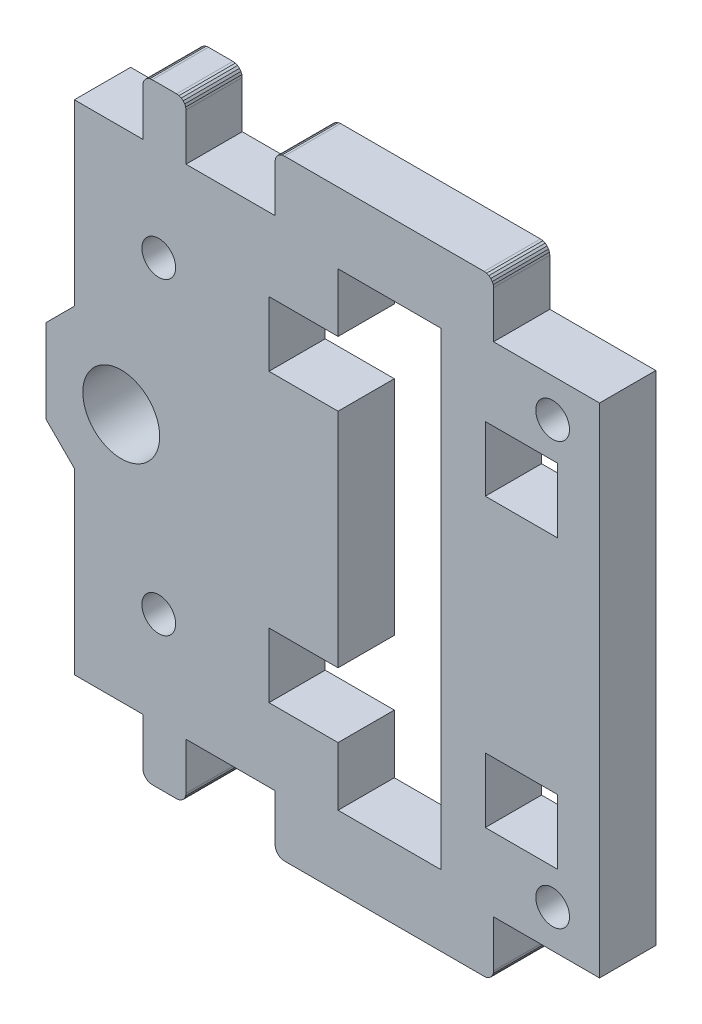
SolidWorks part; units mm, degrees
ref_plane "Plano frontal" through (0, 0, 0) normal (0, 0, 1) x (1, 0, 0)
ref_plane "Plano superior" through (0, 0, 0) normal (0, 1, 0) x (1, 0, 0)
ref_plane "Plano direito" through (0, 0, 0) normal (1, 0, 0) x (0, 0, -1)
sketch "Model" plane through (0, 0, 0) normal (0, 0, 1) x (1, 0, 0)
  line L0 (52.3834, 73.075) -> (52.2835, 72.8339)
  line L1 (38.1893, 9.2156) -> (38.2893, 8.9746)
  line L2 (38.2893, 8.9746) -> (38.4483, 8.7677)
  line L3 (38.4483, 8.7677) -> (38.6553, 8.6089)
  line L4 (27.8494, 36.536) -> (30.8494, 33.536)
  line L5 (27.8494, 45.5141) -> (27.8494, 41.0531)
  line L6 (27.8494, 45.5141) -> (30.8494, 48.5141)
  line L7 (30.8494, 48.5141) -> (30.8494, 67.575)
  line L8 (75.0494, 73.4411) -> (74.8082, 73.541)
  line L9 (75.5153, 72.8339) -> (75.4154, 73.075)
  line L10 (75.5494, 72.575) -> (75.5153, 72.8339)
  line L11 (38.8923, 73.541) -> (39.1512, 73.575)
  line L12 (39.1512, 73.575) -> (41.7508, 73.575)
  line L13 (38.6512, 73.4411) -> (38.8923, 73.541)
  line L14 (52.2494, 9.475) -> (52.2494, 14.475)
  line L15 (52.2494, 9.475) -> (52.2835, 9.2162)
  line L16 (53.2494, 73.575) -> (52.9906, 73.541)
  line L17 (52.9906, 73.541) -> (52.7494, 73.4411)
  line L18 (42.0097, 73.541) -> (41.7508, 73.575)
  line L19 (42.7153, 9.2162) -> (42.6154, 8.975)
  line L20 (42.6154, 8.975) -> (42.4565, 8.7679)
  line L21 (53.2494, 73.575) -> (74.5494, 73.575)
  line L22 (38.6553, 8.6089) -> (38.8964, 8.5091)
  line L23 (38.8964, 8.5091) -> (39.1551, 8.475)
  line L24 (74.8082, 73.541) -> (74.5494, 73.575)
  line L25 (42.6169, 73.075) -> (42.458, 73.2821)
  line L26 (42.458, 73.2821) -> (42.2508, 73.4411)
  line L27 (58.9669, 29.175) -> (58.9669, 52.875)
  line L28 (58.9669, 59.775) -> (58.9669, 66.025)
  line L29 (27.8457, 41.025) -> (27.8494, 40.997)
  line L30 (27.8494, 40.997) -> (27.8494, 36.536)
  line L31 (27.8494, 41.0531) -> (27.8457, 41.025)
  line L32 (30.8494, 14.475) -> (30.8494, 33.536)
  line L33 (30.8494, 14.475) -> (38.1512, 14.475)
  line L34 (86.8494, 14.475) -> (75.5494, 14.475)
  line L35 (75.5494, 14.475) -> (75.5494, 9.475)
  line L36 (42.7494, 14.475) -> (42.7494, 9.475)
  line L37 (86.8494, 67.575) -> (86.8494, 14.475)
  line L38 (86.8494, 67.575) -> (75.5494, 67.575)
  line L39 (51.5984, 59.775) -> (51.5984, 52.875)
  line L40 (51.5984, 52.875) -> (58.9669, 52.875)
  line L41 (74.6669, 59.775) -> (74.6669, 52.875)
  line L42 (82.3669, 59.775) -> (74.6669, 59.775)
  line L43 (74.6669, 52.875) -> (82.3669, 52.875)
  line L44 (82.3669, 52.875) -> (82.3669, 59.775)
  line L45 (58.9669, 29.175) -> (51.5984, 29.175)
  line L46 (74.6669, 29.175) -> (74.6669, 22.275)
  line L47 (51.5984, 22.275) -> (58.9669, 22.275)
  line L48 (51.5984, 29.175) -> (51.5984, 22.275)
  line L49 (82.3669, 22.275) -> (82.3669, 29.175)
  line L50 (74.6669, 22.275) -> (82.3669, 22.275)
  line L51 (82.3669, 29.175) -> (74.6669, 29.175)
  line L52 (42.7494, 9.475) -> (42.7153, 9.2162)
  line L53 (52.2835, 72.8339) -> (52.2494, 72.575)
  line L54 (38.444, 73.2821) -> (38.6512, 73.4411)
  line L55 (38.2851, 73.075) -> (38.444, 73.2821)
  line L56 (38.1852, 72.8339) -> (38.2851, 73.075)
  line L57 (42.7168, 72.8339) -> (42.6169, 73.075)
  line L58 (41.7494, 8.475) -> (39.1551, 8.475)
  line L59 (42.0082, 8.5091) -> (41.7494, 8.475)
  line L60 (75.4154, 73.075) -> (75.2565, 73.2821)
  line L61 (42.4565, 8.7679) -> (42.2494, 8.609)
  line L62 (42.2494, 8.609) -> (42.0082, 8.5091)
  line L63 (75.5494, 67.575) -> (75.5494, 72.575)
  line L64 (30.8494, 67.575) -> (38.1512, 67.575)
  line L65 (52.2494, 67.575) -> (52.2494, 72.575)
  line L66 (74.5494, 8.475) -> (53.2494, 8.475)
  line L67 (52.5423, 73.2821) -> (52.3834, 73.075)
  line L68 (42.7508, 72.575) -> (42.7168, 72.8339)
  line L69 (42.2508, 73.4411) -> (42.0097, 73.541)
  line L70 (69.9669, 16.0251) -> (58.9669, 16.0251)
  line L71 (69.9669, 66.025) -> (69.9669, 16.0251)
  line L72 (58.9669, 66.025) -> (69.9669, 66.025)
  line L73 (58.9669, 16.0251) -> (58.9669, 22.275)
  line L74 (58.9669, 59.775) -> (51.5984, 59.775)
  line L75 (52.7494, 8.609) -> (52.9906, 8.5091)
  line L76 (52.9906, 8.5091) -> (53.2494, 8.475)
  line L77 (74.5494, 8.475) -> (74.8082, 8.5091)
  line L78 (75.2565, 73.2821) -> (75.0494, 73.4411)
  line L79 (52.2835, 9.2162) -> (52.3834, 8.975)
  line L80 (52.3834, 8.975) -> (52.5423, 8.7679)
  line L81 (52.5423, 8.7679) -> (52.7494, 8.609)
  line L82 (74.8082, 8.5091) -> (75.0494, 8.609)
  line L83 (38.1551, 9.4743) -> (38.1893, 9.2156)
  line L84 (75.5153, 9.2162) -> (75.5494, 9.475)
  line L85 (75.0494, 8.609) -> (75.2565, 8.7679)
  line L86 (75.2565, 8.7679) -> (75.4154, 8.975)
  line L87 (52.7494, 73.4411) -> (52.5423, 73.2821)
  line L88 (38.1512, 72.575) -> (38.1852, 72.8339)
  line L89 (42.7508, 72.575) -> (42.7508, 67.575)
  line L90 (75.4154, 8.975) -> (75.5153, 9.2162)
  line L91 (38.1512, 67.575) -> (38.1512, 72.575)
  line L92 (42.7508, 67.575) -> (52.2494, 67.575)
  line L93 (38.1512, 14.475) -> (38.1551, 9.4743)
  line L94 (42.7494, 14.475) -> (52.2494, 14.475)
  circle A0 centre (81.8494, 18.525) radius 1.8
  circle A1 centre (39.8494, 24.575) radius 1.8
  circle A2 centre (35.8494, 41.025) radius 4.1
  circle A3 centre (39.8494, 57.475) radius 1.8
  circle A4 centre (81.8494, 63.525) radius 1.8
extrude "Ressalto-extrusão1" add sketch "Model" along normal blind 6
